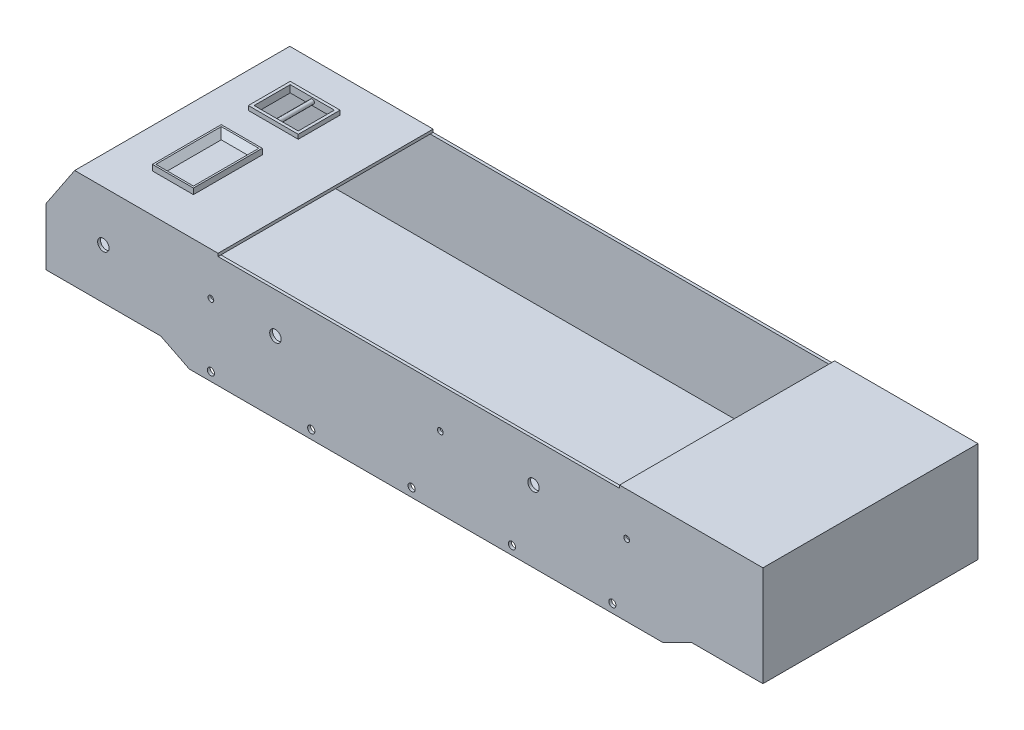
SolidWorks part; units mm, degrees
ref_plane "前视基准面" through (0, 0, 0) normal (0, 0, 1) x (1, 0, 0)
ref_plane "上视基准面" through (0, 0, 0) normal (0, 1, 0) x (1, 0, 0)
ref_plane "右视基准面" through (0, 0, 0) normal (1, 0, 0) x (0, 0, -1)
sketch "草图1" plane through (0, 0, 0) normal (0, 0, 1) x (1, 0, 0)
  line L0 (-250, 5) -> (-230, 35)
  line L1 (-230, 35) -> (-130, 35)
  line L2 (-250, 5) -> (-250, -35)
  line L3 (-250, -35) -> (250, -35)
  line L4 (250, 35) -> (250, -35)
  line L5 (-130, 35) -> (-130, 33)
  line L6 (-130, 33) -> (150, 33)
  line L7 (150, 33) -> (150, 35)
  line L8 (150, 35) -> (250, 35)
  point P0 (0, 0)
  dimension "D1" = 100
  dimension "D2" = 70
  dimension "D3" = 30
  dimension "D4" = 20
  dimension "D5" = 100
  dimension "D6" = 2
extrude "凸台-拉伸1" add sketch "草图1" along normal blind 150
shell "抽壳1" thickness 2 removed face at (10, 33, 75)
sketch "草图3" plane through (0, -35, 0) normal (0, -1, 0) x (1, 0, 0)
  line L0 (250, 150) -> (250, 0) construction
  line L1 (-250, 150) -> (250, 150)
  line L2 (-250, 150) -> (-250, 148)
  line L3 (-250, 148) -> (250, 148)
  line L4 (250, 150) -> (250, 148)
  dimension "D1" = 2
extrude "凸台-拉伸2" add sketch "草图3" along normal blind 10
sketch "草图4" plane through (0, 0, 150) normal (0, 0, 1) x (1, 0, 0)
  line L1 (-150, -45) -> (-170, -35)
  line L2 (250, -35) -> (-250, -35)
  line L3 (250, -35) -> (200, -35)
  line L4 (250, -45) -> (-250, -45) construction
  line L5 (180, -45) -> (200, -35)
  line L6 (250, -45) -> (250, 35) construction
  line L7 (-250, 5) -> (-250, -45) construction
  line L8 (-150, -45) -> (-250, -45)
  line L9 (-250, -45) -> (-250, -35)
  line L10 (180, -45) -> (250, -45)
  line L11 (250, -45) -> (250, -35)
  line L12 (-170, -35) -> (-250, -35)
  dimension "D2" = 50
  dimension "D3" = 20
  dimension "D4" = 80
  dimension "D5" = 20
  dimension "D1" = 10
extrude "切除-拉伸1" cut sketch "草图4" against normal blind 10
ref_plane "基准面1" through (0, 0, 75) normal (0, 0, -1) x (-1, 0, 0)
mirror "镜向1" about plane through (0, 0, 75) normal (0, 0, -1) of "凸台-拉伸2", "切除-拉伸1"
sketch "草图5" plane through (0, 0, 150) normal (0, 0, 1) x (1, 0, 0)
  line L0 (180, -45) -> (-150, -45) construction
  circle A0 centre (-135, -39) radius 2.5
  dimension "D1" = 5
  dimension "D2" = 6
  dimension "D3" = 15
extrude "切除-拉伸2" cut sketch "草图5" against normal blind 2
pattern_linear "阵列(线性)1" count 5 spacing 70 along (1, 0, 0) of "切除-拉伸2"
sketch "草图6" plane through (0, 0, 150) normal (0, 0, 1) x (1, 0, 0)
  line L0 (-250, 5) -> (-250, -35) construction
  line L1 (-170, -35) -> (-250, -35) construction
  circle A0 centre (-135, 5) radius 2
  circle A1 centre (25, 5) radius 2
  circle A2 centre (155, 5) radius 2
  dimension "D1" = 4
  dimension "D4" = 4
  dimension "D6" = 4
  dimension "D2" = 115
  dimension "D3" = 40
  dimension "D5" = 275
  dimension "D7" = 405
extrude "切除-拉伸3" cut sketch "草图6" against normal blind 2
sketch "草图7" plane through (0, 0, 150) normal (0, 0, 1) x (1, 0, 0)
  line L0 (-170, -35) -> (-250, -35) construction
  line L1 (-250, 5) -> (-250, -35) construction
  circle A0 centre (-90, 5) radius 4
  circle A1 centre (90, 5) radius 4
  dimension "D1" = 8
  dimension "D2" = 8
  dimension "D3" = 40
  dimension "D4" = 160
  dimension "D5" = 340
extrude "切除-拉伸4" cut sketch "草图7" against normal blind 2 contours A0 | A1
sketch "草图8" plane through (0, 0, 150) normal (0, 0, 1) x (1, 0, 0)
  line L0 (-250, 5) -> (-250, -35) construction
  line L1 (-170, -35) -> (-250, -35) construction
  circle A0 centre (-210, 0) radius 4
  dimension "D1" = 8
  dimension "D2" = 40
  dimension "D3" = 35
extrude "切除-拉伸5" cut sketch "草图8" against normal up to next
sketch "草图9" plane through (0, 35, 0) normal (0, 1, 0) x (1, 0, 0)
  line L0 (44, -75) -> (-44, -75) construction
  line L5 (-188.2766, -51) -> (-188.2766, -99) construction
  line L6 (-202.5766, -75) -> (-173.9766, -75) construction
  line L7 (-202.5766, -123.2) -> (-202.5766, -75.2)
  line L8 (-202.5766, -75.2) -> (-173.9766, -75.2)
  line L9 (-197.3766, -118) -> (-197.3766, -80.4)
  line L10 (-197.3766, -80.4) -> (-179.1766, -80.4)
  line L11 (-179.1766, -118) -> (-179.1766, -80.4)
  line L12 (-197.3766, -118) -> (-179.1766, -118)
  line L13 (-173.9766, -123.2) -> (-173.9766, -75.2)
  line L14 (-202.5766, -123.2) -> (-173.9766, -123.2)
  line L15 (-130, -150) -> (-230, -150) construction
  point P0 (-188.2766, -75)
  dimension "D1" = 37.6
  dimension "D2" = 5.2
  dimension "D3" = 32
extrude "凸台-拉伸3" add sketch "草图9" along normal blind 4
chamfer "倒角1" distance 4 angle 45 4 edges at (-188.2766, 39, 80.4) (-179.1766, 39, 99.2) (-188.2766, 39, 118) (-197.3766, 39, 99.2)
sketch "草图11" plane through (0, 35, 0) normal (0, 1, 0) x (1, 0, 0)
  line L0 (-203.6766, -51.2) -> (-172.8766, -26) construction
  line L1 (-203.6766, -51.2) -> (-172.8766, -51.2)
  line L2 (-203.6766, -51.2) -> (-203.6766, -26)
  line L3 (-203.6766, -26) -> (-172.8766, -26)
  line L4 (-172.8766, -51.2) -> (-172.8766, -26)
  line L5 (-203.6766, -26) -> (-172.8766, -51.2) construction
  line L10 (-197.3766, -80.4) -> (-197.3766, -118) construction
  line L12 (-130, 0) -> (-230, 0) construction
  line L13 (-205.6766, -53.2) -> (-170.8766, -53.2)
  line L14 (-170.8766, -53.2) -> (-170.8766, -24)
  line L15 (-205.6766, -24) -> (-170.8766, -24)
  line L16 (-205.6766, -53.2) -> (-205.6766, -24)
  point P8 (-188.2766, -38.6)
  dimension "D1" = 25.2
  dimension "D2" = 30.8
  dimension "D3" = 9.1
  dimension "D4" = 26
  dimension "D5" = 2
extrude "凸台-拉伸4" add sketch "草图11" along normal blind 3
extrude "切除-拉伸6" cut sketch "草图11<2>" against normal up to next contours L1 L4 L3 L2 region at (-188.2766, 35, 38.6)
sketch "草图11<2>" plane through (0, 35, 0) normal (0, 1, 0) x (1, 0, 0) same geometry as "草图11"
sketch "草图14" plane through (0, 0, 51.2) normal (0, 0, -1) x (-1, 0, 0)
  line L0 (203.6766, 38) -> (203.6766, 33) construction
  line L2 (203.6766, 38) -> (172.8766, 38) construction
  circle A0 centre (188.2766, 35.5) radius 1.5
  dimension "D1" = 3
  dimension "D2" = 15.4
  dimension "D3" = 2.5
extrude "凸台-拉伸5" add sketch "草图14" along normal up to next
extrude "凸台-拉伸6" add sketch "草图9<2>" against normal blind 3 contours L9 L12 L11 L10 region at (-188.2766, 35, 99.2)
sketch "草图9<2>" plane through (0, 35, 0) normal (0, 1, 0) x (1, 0, 0) same geometry as "草图9"
